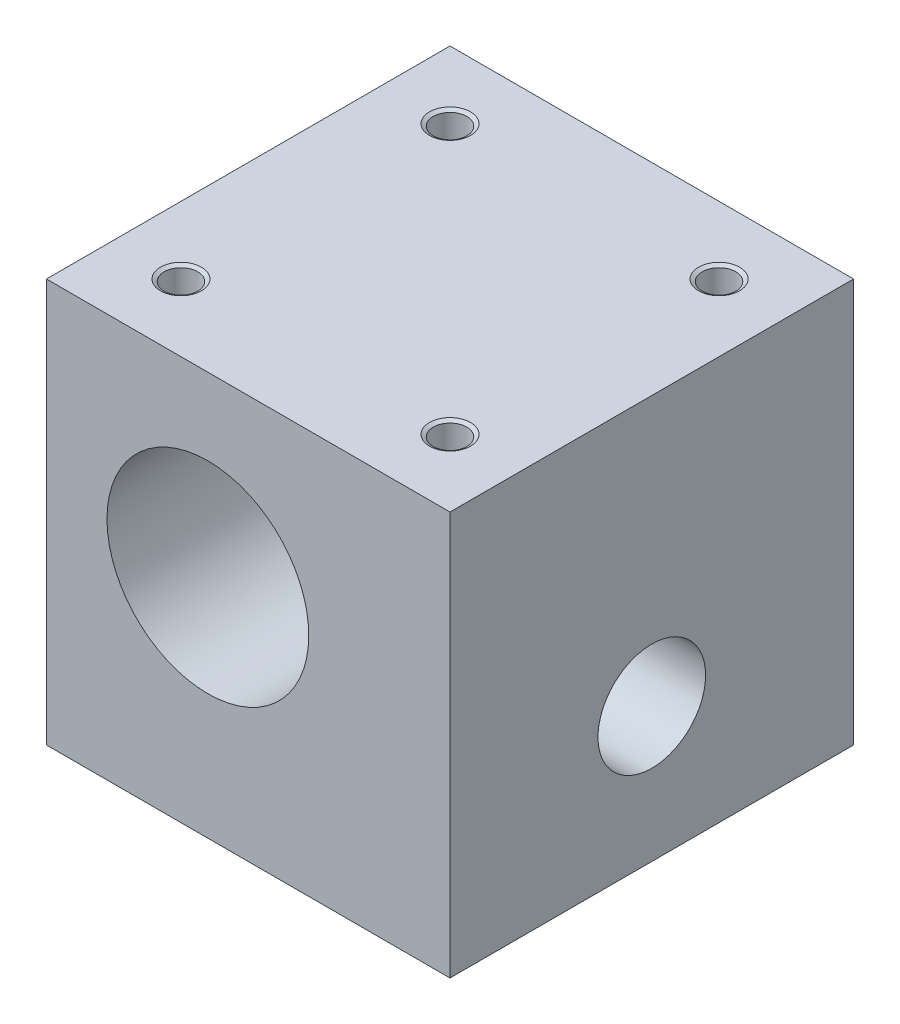
SolidWorks part; units mm, degrees
material "Lega 1060"
ref_plane "Piano frontale" through (0, 0, 0) normal (0, 0, 1) x (1, 0, 0)
ref_plane "Piano superiore" through (0, 0, 0) normal (0, 1, 0) x (1, 0, 0)
ref_plane "Piano destro" through (0, 0, 0) normal (1, 0, 0) x (0, 0, -1)
sketch "Schizzo1" plane through (0, 0, 0) normal (0, 0, 1) x (1, 0, 0)
  line L0 (12, 6.5764) -> (12, 28.444) construction
  line L1 (0, 0) -> (30, 0)
  line L2 (0, 0) -> (0, 30)
  line L3 (0, 30) -> (30, 30)
  line L4 (30, 0) -> (30, 30)
  line L5 (6.315, 16.8) -> (24.6155, 16.8) construction
  circle A0 centre (12, 16.8) radius 7.5
  dimension "D3" = 15
  dimension "D1" = 30
  dimension "D2" = 30
  dimension "D4" = 12
  dimension "D5" = 13.2
extrude "Estrusione-Estrusione1" add sketch "Schizzo1" along normal blind 30
sketch "Schizzo3" plane through (30, 0, 0) normal (1, 0, 0) x (0, 0, -1)
  line L2 (-15, 10.16) -> (-15, 24.3684) construction
  line L3 (-30, 0) -> (-30, 30) construction
  line L4 (0, 0) -> (0, 30) construction
  line L5 (-30, 0) -> (0, 0) construction
  point P0 (-15, 10)
  dimension "D1" = 10
hole_wizard "Foro Ø8.0 (8)-1" positions "Schizzo5" profile "Schizzo4" hole size "Ø8.0" standard "ISO"
sketch "Schizzo5" plane through (30, 0, 0) normal (1, 0, 0) x (0, 0, -1)
  point P0 (-15, 10)
sketch "Schizzo4" plane through (30, 10, 15) normal (0, 1, 0) x (0, 0, -1)
  line L0 (0, 0) -> (0, 12.4034)
  line L1 (0, 12.4034) -> (4, 10)
  line L2 (4, 10) -> (4, 0)
  line L5 (4, 0) -> (0, 0)
  line L10 (0, 12.4034) -> (-4, 10) construction
  line L11 (0, -6.35) -> (0, 107.95) construction
  dimension "Hole Dia." = 8
  dimension "Hole Depth" = 10
  dimension "Drill Angle" = 118
sketch "Schizzo6" plane through (0, 30, 0) normal (0, 1, 0) x (1, 0, 0)
  line L0 (-7.6843, -25) -> (41.504, -25) construction
  line L1 (0, -30) -> (0, 0) construction
  line L2 (30, -30) -> (0, -30) construction
  point P0 (5, -25)
  point P1 (25, -25)
  dimension "D1" = 20
  dimension "D2" = 5
  dimension "D3" = 5
hole_wizard "Foro filettato M3-1" positions "Schizzo8" profile "Schizzo7" tap size "M3" standard "ISO"
sketch "Schizzo8" plane through (0, 30, 0) normal (0, 1, 0) x (1, 0, 0)
  point P0 (5, -25)
  point P3 (25, -25)
sketch "Schizzo7" plane through (5, 30, 25) normal (1, 0, 0) x (0, 0, 1)
  line L0 (0, 0) -> (0, 9.2511)
  line L1 (0, 9.2511) -> (1.25, 8.5)
  line L2 (1.25, 8.5) -> (1.25, 0.1588)
  line L3 (1.25, 0.1588) -> (1.525, 0)
  line L5 (1.525, 0) -> (0, 0)
  line L6 (-1.25, 0.1588) -> (-1.525, 0) construction
  line L10 (0, 9.2511) -> (-1.25, 8.5) construction
  line L11 (0, -6.35) -> (0, 107.95) construction
  dimension "Tap Drill Dia." = 2.5
  dimension "Tap Drill Depth" = 8.5
  dimension "Near C'Sink Dia." = 3.05
  dimension "Near C'Sink Angle" = 120
  dimension "Drill Angle" = 118
cosmetic thread "Filettatura del foro1" parameters "D1"=6, "D2"=3
cosmetic thread "Filettatura del foro2" parameters "D1"=6, "D2"=3
ref_plane "Piano1" through (0, 0, 15) normal (0, 0, 1) x (1, 0, 0)
mirror "Specchia1" about plane through (0, 0, 15) normal (0, 0, 1) of "Foro filettato M3-1"
